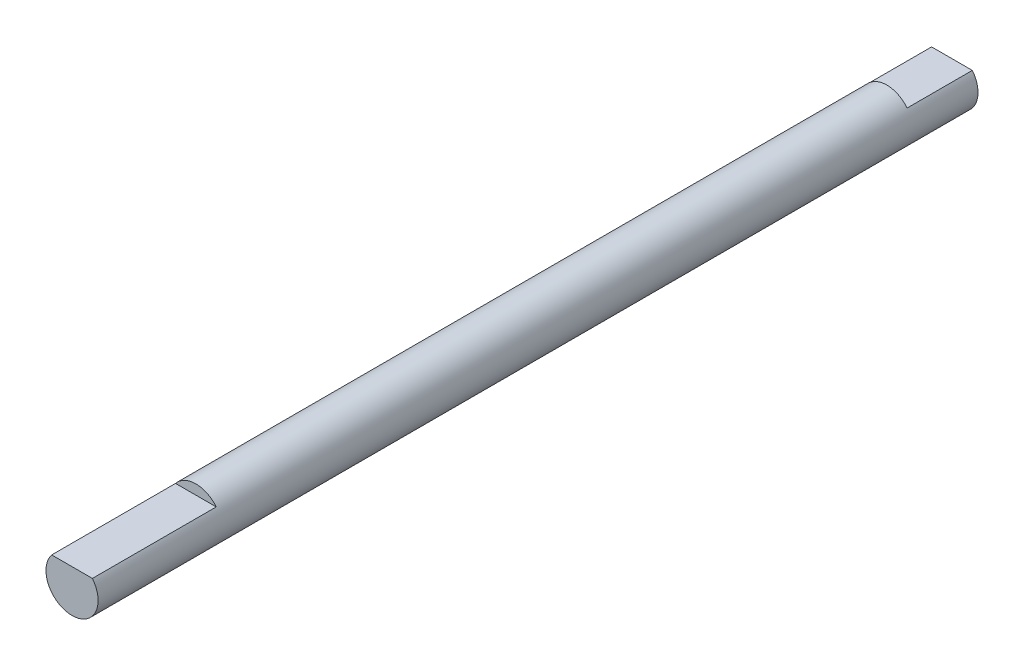
SolidWorks part; units mm, degrees
ref_plane "Front Plane" through (0, 0, 0) normal (0, 0, 1) x (1, 0, 0)
ref_plane "Top Plane" through (0, 0, 0) normal (0, 1, 0) x (1, 0, 0)
ref_plane "Right Plane" through (0, 0, 0) normal (1, 0, 0) x (0, 0, -1)
sketch "Sketch2" plane through (0, 0, 0) normal (0, 0, 1) x (1, 0, 0)
  circle A0 centre (0, 0) radius 4
  dimension "D1" = 8
extrude "Boss-Extrude1" add sketch "Sketch2" along normal blind 135
sketch "Sketch3" plane through (0, 0, 0) normal (0, 0, 1) x (1, 0, 0)
  line L0 (-3.1225, 2.5) -> (3.1225, 2.5)
  circle A0 centre (0, 0) radius 4 construction
  arc A1 (3.1225, 2.5) -> (-3.1225, 2.5) centre (0, 0) ccw
  dimension "D1" = 2.5
extrude "Cut-Extrude1" cut sketch "Sketch3" along normal blind 10
extrude "Cut-Extrude2" cut sketch "Sketch3<2>" against normal blind 19 from surface starting at face at (4, 0, 135)
sketch "Sketch3<2>" plane through (0, 0, 0) normal (0, 0, 1) x (1, 0, 0) same geometry as "Sketch3"
